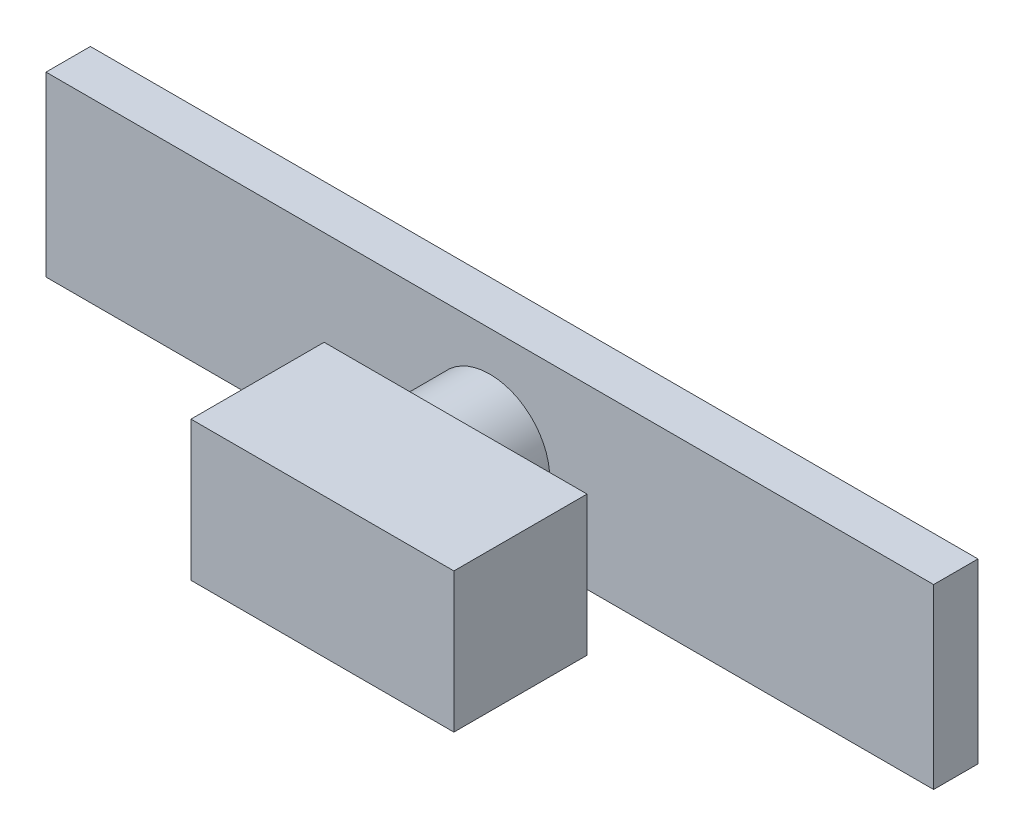
SolidWorks part; units mm, degrees
ref_plane "Front Plane" through (0, 0, 0) normal (0, 0, 1) x (1, 0, 0)
ref_plane "Top Plane" through (0, 0, 0) normal (0, 1, 0) x (1, 0, 0)
ref_plane "Right Plane" through (0, 0, 0) normal (1, 0, 0) x (0, 0, -1)
sketch "Sketch2" plane through (0, 0, 0) normal (0, 0, 1) x (1, 0, 0)
  line L1 (-47.8692, 21.2481) -> (206.1308, 21.2481)
  line L2 (-47.8692, 21.2481) -> (-47.8692, 8.5481)
  line L3 (-47.8692, 8.5481) -> (206.1308, 8.5481)
  line L4 (206.1308, 21.2481) -> (206.1308, 8.5481)
  dimension "D1" = 12.7
  dimension "D2" = 254
extrude "Boss-Extrude1" add sketch "Sketch2" along normal blind 50.8
sketch "Sketch3" plane through (0, 21.2481, 0) normal (0, 1, 0) x (1, 0, 0)
  circle A0 centre (79.1308, -28.4831) radius 17.1408
extrude "Boss-Extrude2" add sketch "Sketch3" along normal blind 19.05
sketch "Sketch4" plane through (0, 40.2981, 0) normal (0, 1, 0) x (1, 0, 0)
  line L1 (50.7675, -8.111) -> (126.0034, -8.111)
  line L2 (50.7675, -8.111) -> (50.7675, -48.0661)
  line L3 (50.7675, -48.0661) -> (126.0034, -48.0661)
  line L4 (126.0034, -8.111) -> (126.0034, -48.0661)
extrude "Boss-Extrude3" add sketch "Sketch4" along normal blind 38.1
scale "Scale2" scale about centroid uniform scaling yes scale factor 0.06
move or copy body "Body-Move/Copy1" bodies to move or copy 105 copy no rotation origin (0, 33.6669, 26.5501) rotation axis (1, 0, 0) rotation angle 90
move or copy body "Body-Move/Copy3" bodies to move or copy 106 copy no translate (-50.8, 0, -50.8)
scale "Scale5" scale about centroid uniform scaling yes scale factor 0.25
move or copy body "Body-Move/Copy9" bodies to move or copy 111 copy no translate (-50.8, 0, 0)
move or copy body "z down" bodies to move or copy 117 copy no translate (0, 0, -25.4)
